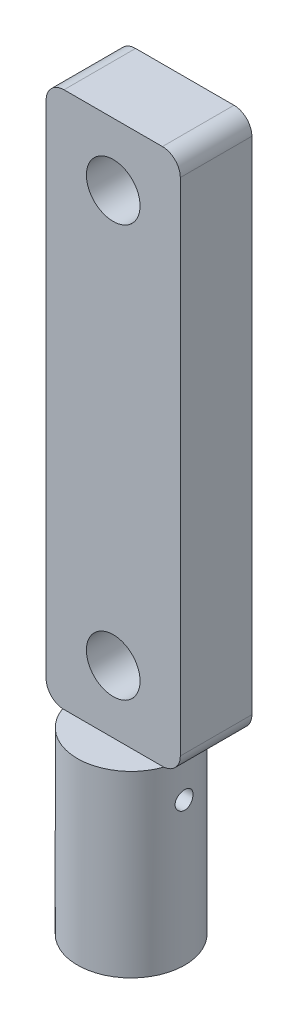
SolidWorks part; units mm, degrees
ref_plane "Front Plane" through (0, 0, 0) normal (0, 0, 1) x (1, 0, 0)
ref_plane "Top Plane" through (0, 0, 0) normal (0, 1, 0) x (1, 0, 0)
ref_plane "Right Plane" through (0, 0, 0) normal (1, 0, 0) x (0, 0, -1)
sketch "Sketch1" plane through (0, 0, 0) normal (0, 0, 1) x (1, 0, 0)
  line L0 (3.75, 26.5) -> (3.75, 3.5) construction
  line L1 (0, 0) -> (7.5, 0)
  line L2 (0, 0) -> (0, 30)
  line L3 (0, 30) -> (7.5, 30)
  line L4 (7.5, 0) -> (7.5, 30)
  circle A0 centre (3.75, 26.5) radius 1.5
  circle A1 centre (3.75, 3.5) radius 1.5
  point P9 (3.75, 15)
  point P10 (0, 15)
  point P11 (3.75, 30)
  dimension "D4" = 3
  dimension "D1" = 30
  dimension "D2" = 7.5
  dimension "D3" = 23
extrude "Boss-Extrude1" add sketch "Sketch1" along normal blind 4
sketch "Sketch2" plane through (0, 0, 0) normal (0, -1, 0) x (1, 0, 0)
  line L0 (0, 4) -> (7.5, 4) construction
  line L1 (0, 0) -> (7.5, 0) construction
  circle A0 centre (3.75, 3) radius 3
  point P2 (0, 0)
  point P5 (3.75, 4)
  point P8 (0, 0)
  dimension "D1" = 6
extrude "Boss-Extrude2" add sketch "Sketch2" along normal blind 10
sketch "Sketch3" plane through (7.5, 0, 0) normal (1, 0, 0) x (0, 0, -1)
  line L0 (-4, 0) -> (0, 0) construction
  line L1 (-2, 0) -> (-2, -2) construction
  line L2 (-2, -2) -> (-3, -2) construction
  circle A0 centre (-3, -2) radius 0.5
  point P7 (-2, 0)
  dimension "D2" = 1
  dimension "D1" = 2
extrude "Cut-Extrude1" cut sketch "Sketch3" against normal through all
fillet "Fillet8" radius 1 4 edges at (7.5, 0, 2) (0, 0, 2) (0, 30, 2) (7.5, 30, 2)
